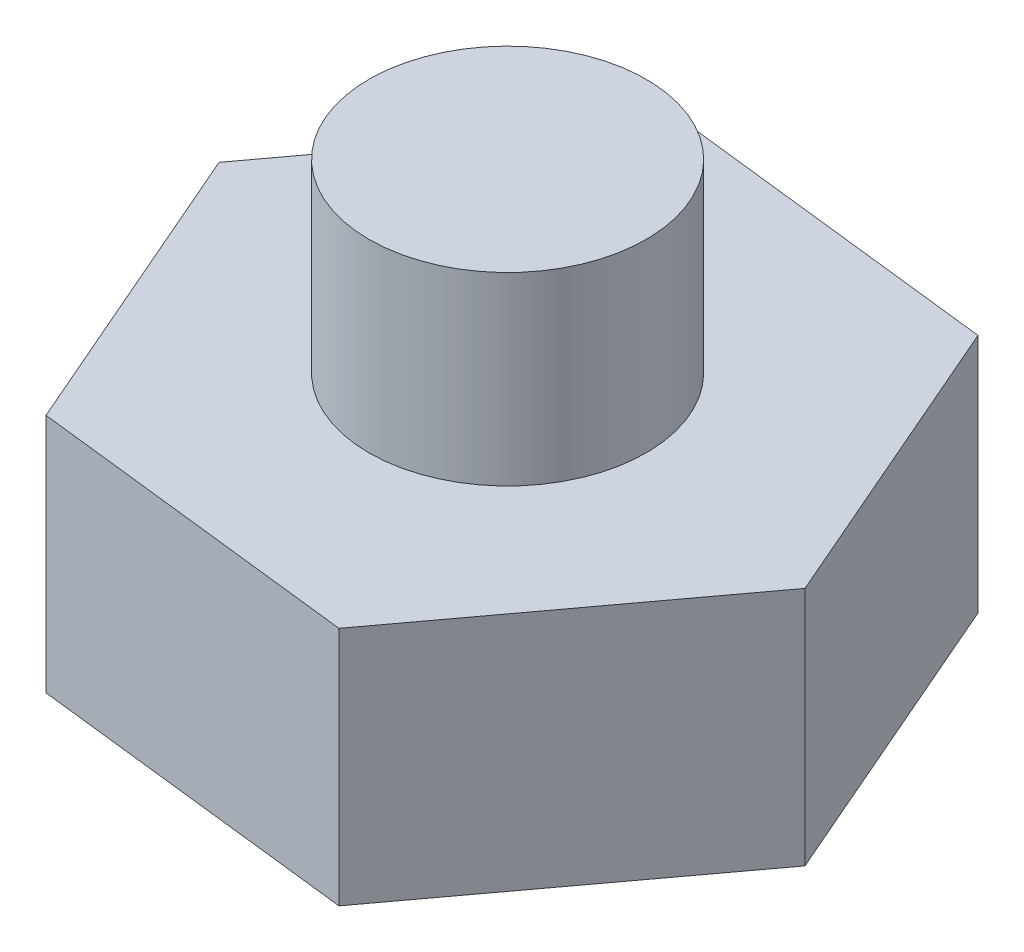
SolidWorks part; units mm, degrees
ref_plane "Front Plane" through (0, 0, 0) normal (0, 0, 1) x (1, 0, 0)
ref_plane "Top Plane" through (0, 0, 0) normal (0, 1, 0) x (1, 0, 0)
ref_plane "Right Plane" through (0, 0, 0) normal (1, 0, 0) x (0, 0, -1)
sketch "Sketch2" plane through (0, 0, 0) normal (0, 1, 0) x (1, 0, 0)
  line L1 (35.85, -82.6477) -> (89.5, -10.2768)
  line L2 (89.5, -10.2768) -> (53.65, 72.3709)
  line L3 (53.65, 72.3709) -> (-35.85, 82.6477)
  line L4 (-35.85, 82.6477) -> (-89.5, 10.2768)
  line L5 (-89.5, 10.2768) -> (-53.65, -72.3709)
  line L6 (-53.65, -72.3709) -> (35.85, -82.6477)
  circle A0 centre (0, 0) radius 78.0186 construction
  circle A1 centre (-1.1915, 0) radius 37.5
  dimension "D2" = 75
  dimension "D1" = 179
extrude "Boss-Extrude1" add sketch "Sketch2" along normal blind 65
extrude "Boss-Extrude2" add sketch "Sketch2<2>" along normal blind 115 contours A1 region at (-1.1915, 0, 0)
sketch "Sketch2<2>" plane through (0, 0, 0) normal (0, 1, 0) x (1, 0, 0) same geometry as "Sketch2"
